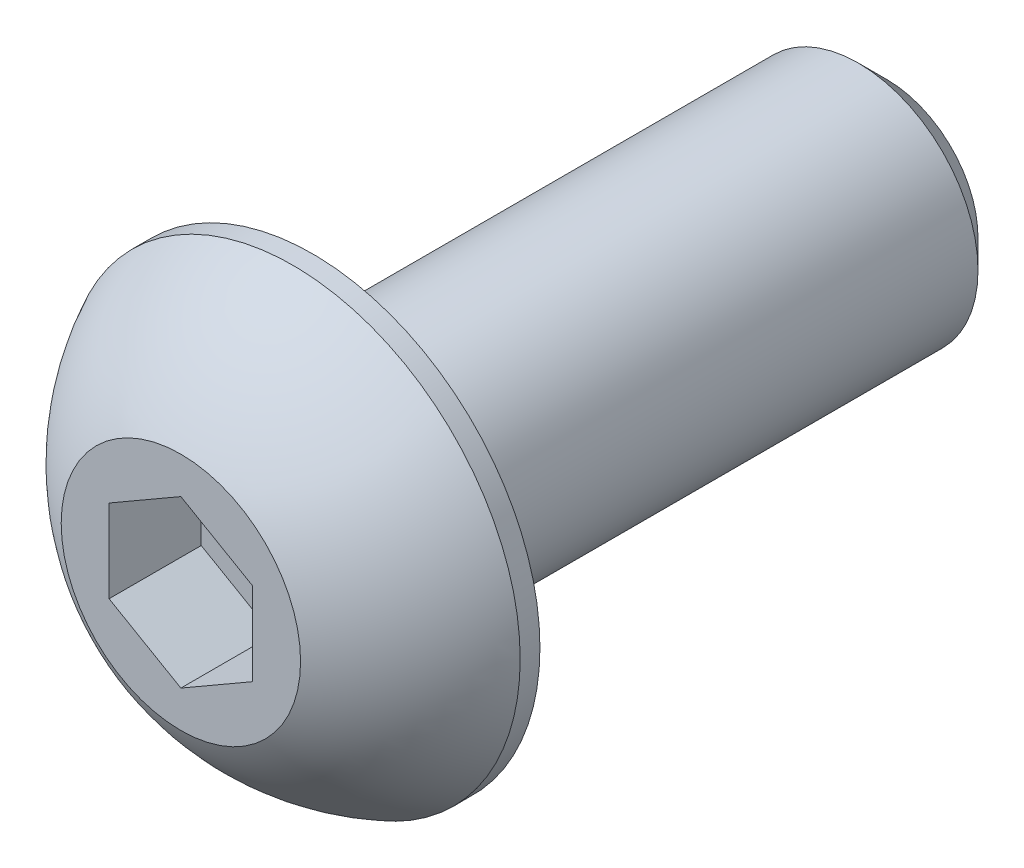
SolidWorks part; units mm, degrees
ref_plane "Front" through (0, 0, 0) normal (0, 0, 1) x (1, 0, 0)
ref_plane "Top" through (0, 0, 0) normal (0, 1, 0) x (1, 0, 0)
ref_plane "Right" through (0, 0, 0) normal (1, 0, 0) x (0, 0, -1)
sketch "Sketch1" plane through (0, 0, 0) normal (1, 0, 0) x (0, 0, -1)
  line L2 (2.75, 2.5) -> (14.75, 2.5)
  line L3 (14.75, 2.5) -> (14.75, 0)
  line L4 (14.75, 0) -> (2.75, 0)
  line L6 (2.3375, 4.75) -> (2.75, 4.75) construction
  line L7 (14.75, 2.5) -> (14.75, -2.5) construction
  line L8 (0, 0) -> (2.75, 0) construction
  line L9 (2.75, 4.75) -> (2.75, -4.75) construction
  line L11 (2.75, 2.5) -> (2.75, 0)
  line L13 (0, 1.5) -> (0, -1.5) construction
  line L14 (0, 1.5) -> (0, 2.5) construction
  arc A3 (0, 2.5) -> (2.3375, 4.75) centre (4.6581, 0) cw construction
  dimension "D1" = 0.4125
revolve "Revolve1" add sketch "Sketch1" angle 360 mid plane about L4
sketch "Sketch3" plane through (0, 0, -14.75) normal (0, 0, -1) x (-1, 0, 0)
  circle A0 centre (0, 0) radius 2.5
curve "Helix/Spiral1" [suppressed] pitch 0.8 height 12.8 turns 16
chamfer "Chamfer1" distance 0.6 angle 45 1 edges at (0, 2.5, -14.75)
sketch "Sketch7" plane through (0, 0, 0) normal (1, 0, 0) x (0, 0, -1)
  line L6 (2.3375, 4.75) -> (2.75, 4.75) construction
  line L8 (0, 0) -> (2.75, 0) construction
  line L11 (2.75, 4.75) -> (2.75, -4.75) construction
  line L12 (2.3375, 4.75) -> (2.75, 4.75)
  line L13 (0, 0) -> (2.75, 0)
  line L14 (0, 1.5) -> (0, -1.5) construction
  line L15 (2.75, 4.75) -> (2.75, 0)
  line L16 (0, 2.5) -> (0, 0)
  arc A2 (2.3375, 4.75) -> (0, 2.5) centre (4.6581, 0) ccw construction
  arc A3 (2.3375, 4.75) -> (0, 2.5) centre (4.6581, 0) ccw
revolve "Revolve2" add sketch "Sketch7" angle 360 mid plane about L13
sketch "Sketch5" plane through (0, 0, 0) normal (0, 0, 1) x (1, 0, 0)
  line L1 (1.5, -0.866) -> (1.5, 0.866)
  line L2 (1.5, 0.866) -> (0, 1.7321)
  line L3 (0, 1.7321) -> (-1.5, 0.866)
  line L4 (-1.5, 0.866) -> (-1.5, -0.866)
  line L5 (-1.5, -0.866) -> (0, -1.7321)
  line L6 (0, -1.7321) -> (1.5, -0.866)
  circle A0 centre (0, 0) radius 1.5 construction
extrude "Cut-Extrude2" cut sketch "Sketch5" against normal blind 1.925
sketch "Sketch6" plane through (0, 0, 0) normal (0, 0, 1) x (1, 0, 0)
  circle A0 centre (0, 0) radius 1.7321
extrude "Cut-Extrude3" [suppressed] cut sketch "Sketch6" against normal blind 1.925 draft 45
sketch "Sketch2" plane through (0, 0, 0) normal (1, 0, 0) x (0, 0, -1)
  line L0 (14.15, 2.5) -> (14.85, 2.5)
  line L1 (14.85, 2.5) -> (14.55, 1.9804)
  line L2 (14.55, 1.9804) -> (14.45, 1.9804)
  line L3 (14.45, 1.9804) -> (14.15, 2.5)
  line L4 (14.3, 2.2402) -> (14.7, 2.2402) construction
  dimension "D1" = 60
  dimension "D2" = 0.1
  dimension "D3" = 0.4
sweep "Cut-Sweep1" [suppressed] cut profiles "Sketch2" path "Helix/Spiral1"
sketch "Sketch10" plane through (0, 0, 0) normal (1, 0, 0) x (0, 0, -1)
  line L0 (14.75, 2.5) -> (14.75, -2.5) construction
  point P0 (13.55, -2.5)
  dimension "D1" = 1.2
ref_axis "Center Axis 1" through (0, 0, -8.1113) along (0, 0, 1)
ref_plane "Contact Plane 1" through (0, 0, -2.75) normal (0, 0, -1) x (-1, 0, 0)
ref_plane "Contact Plane 2" through (0, 0, 0) normal (0, 0, 1) x (1, 0, 0)
equation "\"D3@Helix/Spiral1\" = \"Lg@Sketch1\" + \"D4@Helix/Spiral1\""
equation "\"D2@Sketch2\" = \"D4@Helix/Spiral1\" * .125"
equation "\"D3@Sketch2\" = \"D4@Helix/Spiral1\" * .5"
equation "\"D1@Chamfer1\" = \"D4@Helix/Spiral1\" * .75"
equation "\"D1@Cut-Extrude2\" = \"Head Ht@Sketch1\" * .7"
equation "\"D1@Sketch1\" = \"Head Ht@Sketch1\" * .15"
equation "\"D1@Sketch10\" = \"D4@Helix/Spiral1\" * 1.5"
equation "\"D1@Cut-Extrude3\" = \"D1@Cut-Extrude2\""
